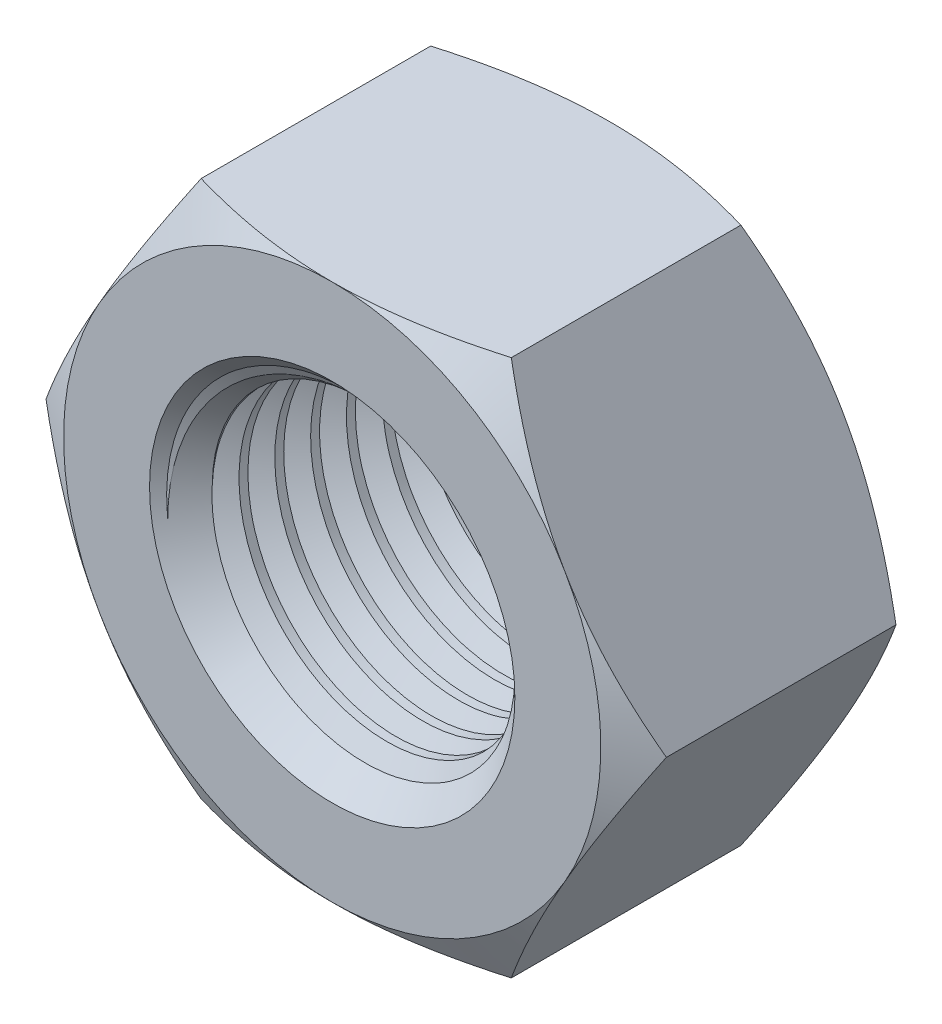
SolidWorks part; units mm, degrees
ref_plane "Front" through (0, 0, 0) normal (0, 0, 1) x (1, 0, 0)
ref_plane "Top" through (0, 0, 0) normal (0, 1, 0) x (1, 0, 0)
ref_plane "Right" through (0, 0, 0) normal (1, 0, 0) x (0, 0, -1)
sketch "Çizim1" plane through (0, 0, 0) normal (0, 0, 1) x (1, 0, 0)
  line L1 (34.641, 0) -> (17.3205, 30)
  line L2 (17.3205, 30) -> (-17.3205, 30)
  line L3 (-17.3205, 30) -> (-34.641, 0)
  line L4 (-34.641, 0) -> (-17.3205, -30)
  line L5 (-17.3205, -30) -> (17.3205, -30)
  line L6 (17.3205, -30) -> (34.641, 0)
  circle A0 centre (0, 0) radius 30 construction
  point P1 (0, 0)
  dimension "D1" = 60
extrude "Yükseklik-Ekstrüzyon1" add sketch "Çizim1" along normal blind 31
sketch "Çizim2" plane through (0, 0, 31) normal (0, 0, 1) x (1, 0, 0)
  circle A0 centre (0, 0) radius 30
extrude "Kes-Ekstrüzyon1" cut sketch "Çizim2" against normal blind 31 draft 60 flip side to cut
sketch "Çizim3" plane through (0, 0, 0) normal (0, 0, -1) x (-1, 0, 0)
  circle A0 centre (0, 0) radius 30
extrude "Kes-Ekstrüzyon2" cut sketch "Çizim3" against normal blind 31 draft 60 flip side to cut
sketch "Çizim4" plane through (0, 0, 31) normal (0, 0, 1) x (1, 0, 0)
  circle A0 centre (0, 0) radius 16.9
  dimension "D1" = 33.8
extrude "Kes-Ekstrüzyon3" cut sketch "Çizim4" against normal blind 31
chamfer "Pah1" distance 3.5 angle 45 2 edges at (16.9, 0, 0) (16.9, 0, 31)
sketch "Çizim5" plane through (0, 0, 0) normal (0, 0, -1) x (-1, 0, 0)
  circle A0 centre (0, 0) radius 16.9
curve "Helis/Spiral1" pitch 4 height 38 radius 16.9 centre (0, 0, 0) axis (0, 0, 1) start towards (1, 0, 0)
ref_plane "Düzlem1" through (-16.9, 0, 38) normal (0, -0.9993, 0.0376) x (-1, 0, 0)
sketch "Çizim6" plane through (-16.9, 0, 38) normal (0, -0.9993, 0.0376) x (-1, 0, 0)
  line L0 (-0.8526, 1.9933) -> (-0.8526, -1.9933)
  line L1 (2.6, 0) -> (-0.8526, 1.9933)
  line L3 (-0.8526, -1.9933) -> (2.6, 0)
  line L5 (-1.3, 2.2517) -> (-1.3, 0) [skipped]
  circle A0 centre (0, 0) radius 1.3 construction
  dimension "D1" = 2.6
sweep "Kes-Süpür1" cut profiles "Çizim6" path "Helis/Spiral1" align with end faces yes
